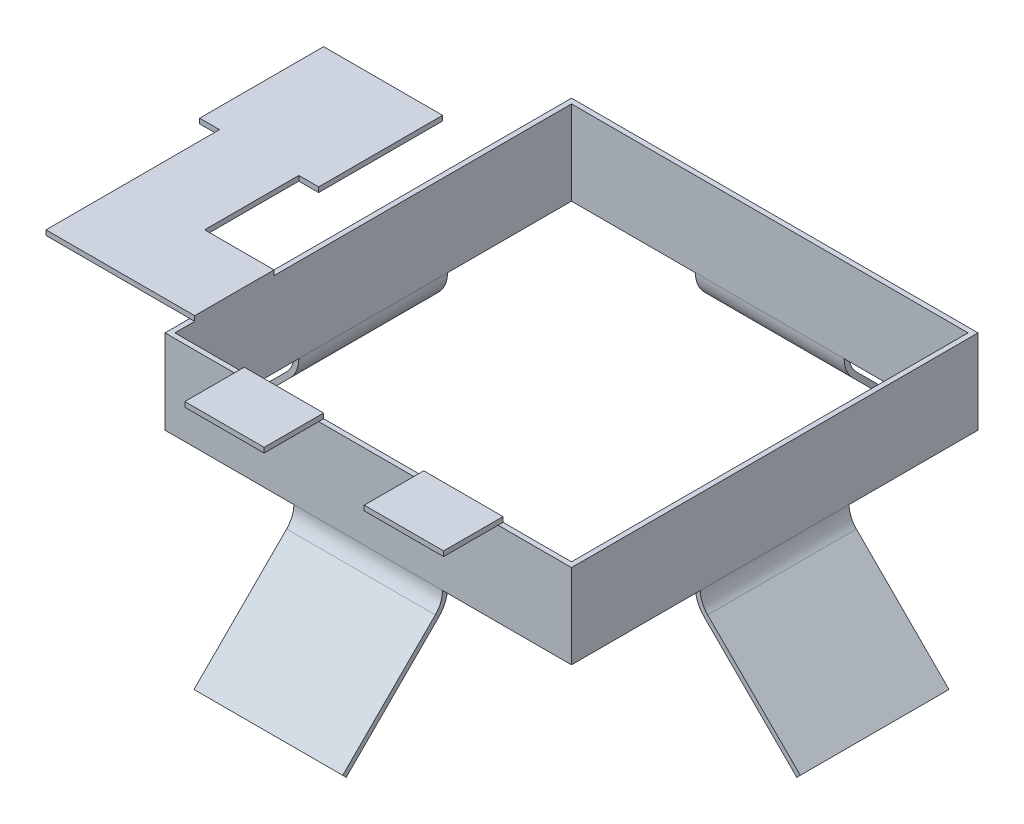
SolidWorks part; units mm, degrees
ref_plane "Front Plane" through (0, 0, 0) normal (0, 0, 1) x (1, 0, 0)
ref_plane "Top Plane" through (0, 0, 0) normal (0, 1, 0) x (1, 0, 0)
ref_plane "Right Plane" through (0, 0, 0) normal (1, 0, 0) x (0, 0, -1)
sketch "Sketch1" plane through (0, 0, 0) normal (0, 1, 0) x (1, 0, 0)
  line L1 (-4, 4) -> (4, 4)
  line L2 (-4, 4) -> (-4, -4)
  line L3 (-4, -4) -> (4, -4)
  line L4 (4, 4) -> (4, -4)
  line L5 (-4.1, 4.1) -> (4.1, 4.1)
  line L6 (-4.1, 4.1) -> (-4.1, -4.1)
  line L7 (-4.1, -4.1) -> (4.1, -4.1)
  line L8 (4.1, 4.1) -> (4.1, -4.1)
  dimension "D1" = 4
  dimension "D2" = 4
  dimension "D3" = 4
  dimension "D4" = 4
  dimension "D5" = 0.1
  dimension "D6" = 0.1
  dimension "D7" = 0.1
  dimension "D8" = 0.1
extrude "Boss-Extrude1" add sketch "Sketch1" along normal blind 1.7
ref_plane "Plane1" through (0, 0, 0) normal (-1, 0, 0) x (0, 0, 1)
sketch "Sketch2" plane through (0, 0, 0) normal (-1, 0, 0) x (0, 0, 1)
  line L0 (6.1152, -2.2223) -> (4.2464, -0.3536)
  line L1 (-4.1, 0) -> (4.1, 0) construction
  line L2 (4.1, 1.7) -> (4.1, 0) construction
  line L3 (4.1757, -0.4243) -> (6.0445, -2.2931)
  line L4 (6.1152, -2.2223) -> (6.0445, -2.2931)
  line L5 (4.1, 0) -> (-4.1, 0) construction
  line L7 (4, 0) -> (4, 0.0229)
  line L8 (4.1, 0) -> (4.1, 0.0229)
  line L9 (4, 0.0229) -> (4.1, 0.0229)
  arc A0 (4.1, 0) -> (4.2464, -0.3536) centre (4.6, 0) ccw
  arc A1 (4, 0) -> (4.1757, -0.4243) centre (4.6, 0) ccw
  dimension "D2" = 1
  dimension "D3" = 0.5
  dimension "D8" = 4.6
  dimension "D4" = 0.1
  dimension "D1" = 225
  dimension "D5" = 90
  dimension "D6" = 90
  dimension "D9" = 0.1
  dimension "D10" = 0
  dimension "D11" = 0
extrude "Boss-Extrude2" add sketch "Sketch2" along normal blind 1.5 and the other way blind 1.5 contours A1 L3 L4 L0 A0 L8 L9 L7
ref_plane "Plane2" through (0, 0, 0) normal (0, 0, 1) x (1, 0, 0)
ref_axis "Axis1" through (0, -0.1, 0) along (0, 1, 0)
pattern_circular "CirPattern1" count 4 every 90 about axis through (0, -0.1, 0) along (0, 1, 0) of "Boss-Extrude2"
sketch "Sketch3" plane through (0, 1.7, 0) normal (0, 1, 0) x (1, 0, 0)
  line L0 (-4, 4) -> (-4, -4) construction
  line L1 (-4, -3.6) -> (-5.4, -3.6)
  line L2 (-4, -3.6) -> (-4, -2)
  line L3 (-4, -2) -> (-5.4, -2)
  line L5 (-4.1, -4.1) -> (4.1, -4.1) construction
  line L9 (-5.4, -2) -> (-5.4, -0.1)
  line L11 (-5.0001, 2.4) -> (-5.4, 2.4)
  line L12 (-5.0001, 2.4) -> (-5.0001, -0.1)
  line L14 (-7.4001, 2.4) -> (-7.4001, -0.1)
  line L15 (-6.2, -0.1) -> (-6.2, -0.6) construction
  line L16 (-7, 2.4) -> (-7.4001, 2.4)
  line L17 (-7, 2.4) -> (-5.4, 2.4)
  line L18 (-7, -0.1) -> (-7, -3.6)
  line L19 (-7, -0.1) -> (-7.4001, -0.1)
  line L20 (-5.4, -0.1) -> (-5.0001, -0.1)
  line L21 (-7, -3.6) -> (-5.4, -3.6)
  dimension "D1" = 1.6
  dimension "D2" = 3
  dimension "D3" = 1.6
  dimension "D4" = 0.5
  dimension "D5" = 6
  dimension "D6" = 2.5
  dimension "D7" = 2.4
extrude "Boss-Extrude3" add sketch "Sketch3" along normal blind 0.1
sketch "Sketch4" plane through (0, 1.7, 0) normal (0, 1, 0) x (1, 0, 0)
  line L0 (-4, -4) -> (4, -4) construction
  line L1 (-1, -4) -> (-2.6, -4)
  line L2 (-1, -4) -> (-1, -5.2)
  line L3 (-1, -5.2) -> (-2.6, -5.2)
  line L4 (-2.6, -4) -> (-2.6, -5.2)
  line L5 (0, -3.51) -> (0, -5.5025) construction
  line L6 (1.0194, -4) -> (2.6194, -4)
  line L7 (1.0194, -4) -> (1.0194, -5.2)
  line L8 (1.0194, -5.2) -> (2.6194, -5.2)
  line L9 (2.6194, -4) -> (2.6194, -5.2)
  line L10 (0, 0.935) -> (0, -0.935) construction
  dimension "D1" = 1
  dimension "D2" = 1.0194
  dimension "D3" = 1.6
  dimension "D4" = 1.6
  dimension "D5" = 1.2
  dimension "D6" = 1.2
extrude "Boss-Extrude4" add sketch "Sketch4" along normal blind 0.1
